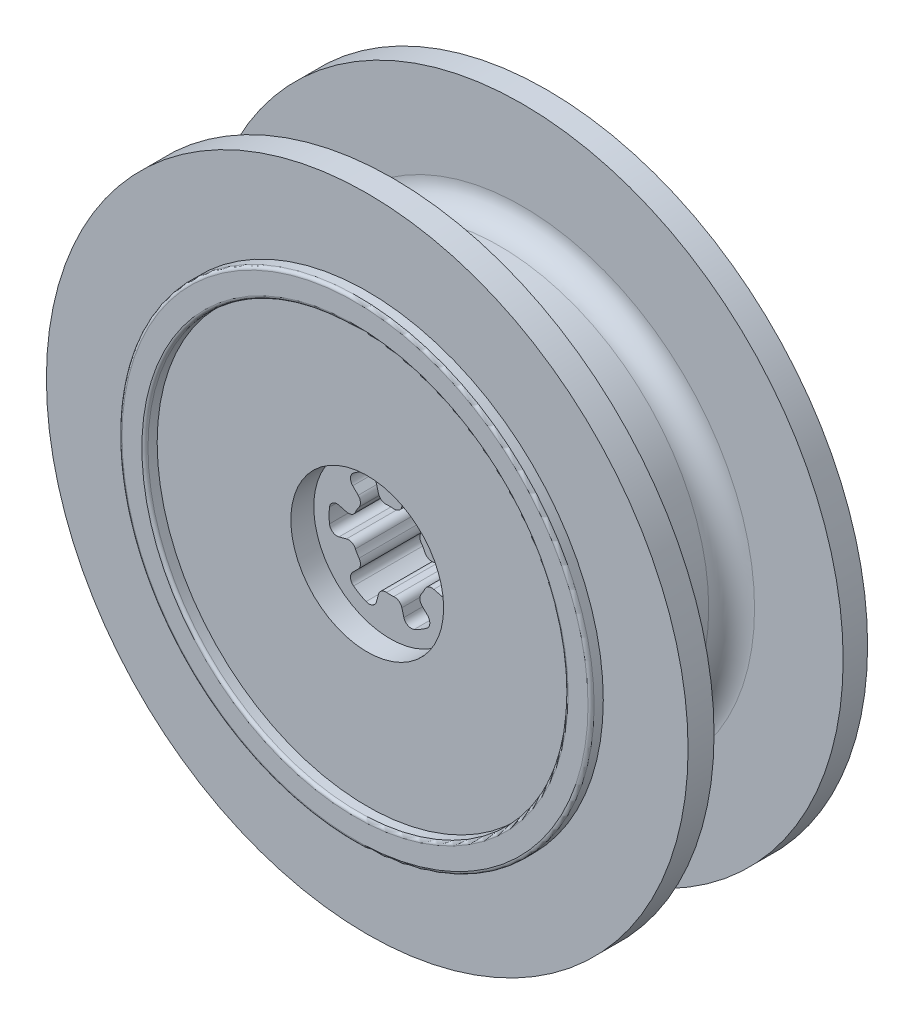
SolidWorks part; units mm, degrees
ref_plane "Front Plane" through (0, 0, 0) normal (0, 0, 1) x (1, 0, 0)
ref_plane "Top Plane" through (0, 0, 0) normal (0, 1, 0) x (1, 0, 0)
ref_plane "Right Plane" through (0, 0, 0) normal (1, 0, 0) x (0, 0, -1)
sketch "Sketch1" plane through (0, 0, 0) normal (0, 0, 1) x (1, 0, 0)
  line L1 (0.647, 2.4148) -> (1.0353, 3.8637)
  line L3 (1.7678, 1.7678) -> (2.8284, 2.8284)
  line L5 (2.4148, 0.647) -> (3.8637, 1.0353)
  line L7 (2.4148, -0.647) -> (3.8637, -1.0353)
  line L9 (1.7678, -1.7678) -> (2.8284, -2.8284)
  line L11 (0.647, -2.4148) -> (1.0353, -3.8637)
  line L13 (-0.647, -2.4148) -> (-1.0353, -3.8637)
  line L15 (-1.7678, -1.7678) -> (-2.8284, -2.8284)
  line L17 (-2.4148, -0.647) -> (-3.8637, -1.0353)
  line L19 (-2.4148, 0.647) -> (-3.8637, 1.0353)
  line L21 (-1.7678, 1.7678) -> (-2.8284, 2.8284)
  line L23 (-0.647, 2.4148) -> (-1.0353, 3.8637)
  circle A0 centre (0, 0) radius 21
  circle A1 centre (0, 0) radius 4
  arc A2 (0.647, 2.4148) -> (-0.647, 2.4148) centre (0, 0) ccw
  arc A3 (2.4148, 0.647) -> (1.7678, 1.7678) centre (0, 0) ccw
  arc A4 (1.7678, -1.7678) -> (2.4148, -0.647) centre (0, 0) ccw
  arc A5 (-0.647, -2.4148) -> (0.647, -2.4148) centre (0, 0) ccw
  arc A6 (-2.4148, -0.647) -> (-1.7678, -1.7678) centre (0, 0) ccw
  arc A7 (-1.7678, 1.7678) -> (-2.4148, 0.647) centre (0, 0) ccw
  circle A8 centre (0, 0) radius 13.75
  circle A9 centre (0, 0) radius 15.45
  point P31 (0, 0)
  dimension "D1" = 42
  dimension "D2" = 8
  dimension "D3" = 2.5
  dimension "D4" = 27.5
  dimension "D5" = 30.9
extrude "Boss-Extrude1" add sketch "Sketch1" along normal blind 1.7 contours A5 L13 A1 L11 | A6 L17 A1 L15 | A7 L21 A1 L19 | A2 L1 A1 L23 | A0 A9 | A9 A8 | A3 L5 A1 L3 | A8 A1 | A4 L9 A1 L7 region at (0, 3.27, 0) region at (2.8319, 1.635, 0) region at (-2.8319, 1.635, 0) region at (2.8319, -1.635, 0) region at (-2.8319, -1.635, 0) region at (0, -3.27, 0) region at (-20.406, 0, 0) region at (-13.3611, 0, 0) region at (-15.013, 0, 0)
extrude "Boss-Extrude2" add sketch "Sketch1<7>" along normal blind 0.75 contours A9 A8 region at (-15.013, 0, 0)
sketch "Sketch1<7>" plane through (0, 0, 0) normal (0, 0, 1) x (1, 0, 0) same geometry as "Sketch1"
sketch "Sketch3" plane through (0, 0, 0) normal (0, 0, -1) x (-1, 0, 0)
  circle A0 centre (0, 0) radius 13.7
  circle A1 centre (0, 0) radius 12
  dimension "D1" = 27.4
  dimension "D2" = 24
extrude "Boss-Extrude3" add sketch "Sketch3" along normal blind 8.45
sketch "Sketch6" plane through (0, 0, -8.45) normal (0, 0, -1) x (-1, 0, 0)
  circle A0 centre (0, 0) radius 21
  circle A1 centre (0, 0) radius 12.0174
extrude "Boss-Extrude5" add sketch "Sketch6" along normal blind 1.6
sketch "Sketch7" plane through (0, 0, 1.7) normal (0, 0, 1) x (1, 0, 0)
  line L0 (0.647, 2.4148) -> (1.0353, 3.8637)
  line L1 (-0.647, 2.4148) -> (-1.0353, 3.8637)
  line L2 (1.7678, 1.7678) -> (2.8284, 2.8284)
  line L3 (1.7678, 1.7678) -> (2.8284, 2.8284) construction
  line L4 (2.4148, 0.647) -> (3.8637, 1.0353)
  line L5 (-1.7678, 1.7678) -> (-2.8284, 2.8284)
  line L6 (-2.4148, 0.647) -> (-3.8637, 1.0353)
  line L7 (-2.4148, -0.647) -> (-3.8637, -1.0353)
  line L8 (-1.7678, -1.7678) -> (-2.8284, -2.8284)
  line L9 (2.4148, -0.647) -> (3.8637, -1.0353)
  line L10 (2.8284, -2.8284) -> (1.7678, -1.7678)
  line L11 (1.7678, -1.7678) -> (2.8284, -2.8284) construction
  line L12 (0.647, -2.4148) -> (1.0353, -3.8637)
  line L13 (-1.0353, -3.8637) -> (-0.647, -2.4148)
  circle A0 centre (0, 0) radius 5
  circle A1 centre (0, 0) radius 2.5
  circle A2 centre (0, 0) radius 4
  arc M1 (0.647, -2.4148) -> (-0.647, -2.4148) centre (0, 0) cw
  line M2 (-0.647, -2.4148) -> (-1.0353, -3.8637)
  arc M3 (-1.0353, -3.8637) -> (-2.8284, -2.8284) centre (0, 0) cw
  line M4 (-2.8284, -2.8284) -> (-1.7678, -1.7678)
  arc M5 (-1.7678, -1.7678) -> (-2.4148, -0.647) centre (0, 0) cw
  line M6 (-2.4148, -0.647) -> (-3.8637, -1.0353)
  arc M7 (-3.8637, -1.0353) -> (-3.8637, 1.0353) centre (0, 0) cw
  line M8 (-3.8637, 1.0353) -> (-2.4148, 0.647)
  arc M9 (-2.4148, 0.647) -> (-1.7678, 1.7678) centre (0, 0) cw
  line M10 (-1.7678, 1.7678) -> (-2.8284, 2.8284)
  arc M11 (-2.8284, 2.8284) -> (-1.0353, 3.8637) centre (0, 0) cw
  line M12 (-1.0353, 3.8637) -> (-0.647, 2.4148)
  arc M13 (-0.647, 2.4148) -> (0.647, 2.4148) centre (0, 0) cw
  line M14 (0.647, 2.4148) -> (1.0353, 3.8637)
  arc M15 (1.0353, 3.8637) -> (2.8284, 2.8284) centre (0, 0) cw
  line M16 (2.8284, 2.8284) -> (1.7678, 1.7678)
  arc M17 (1.7678, 1.7678) -> (2.4148, 0.647) centre (0, 0) cw
  line M18 (2.4148, 0.647) -> (3.8637, 1.0353)
  arc M19 (3.8637, 1.0353) -> (3.8637, -1.0353) centre (0, 0) cw
  line M20 (3.8637, -1.0353) -> (2.4148, -0.647)
  arc M21 (2.4148, -0.647) -> (1.7678, -1.7678) centre (0, 0) cw
  line M22 (1.7678, -1.7678) -> (2.8284, -2.8284)
  arc M23 (2.8284, -2.8284) -> (1.0353, -3.8637) centre (0, 0) cw
  line M24 (1.0353, -3.8637) -> (0.647, -2.4148)
  dimension "D1" = 10
  dimension "D2" = 5
  dimension "D3" = 8
extrude "Boss-Extrude6" add sketch "Sketch7" against normal blind 16.85 contours A0 A2 M19 M23 M3 M7 M11 M15 | A2 M14 M12 M13 | A2 M18 M16 M17 | A2 M22 M20 M21 | A2 M2 M24 M1 | A2 M6 M4 M5 | A2 M10 M8 M9 region at (0, 3.27, 1.7) region at (2.8319, 1.635, 1.7) region at (-2.8319, 1.635, 1.7) region at (2.8319, -1.635, 1.7) region at (-2.8319, -1.635, 1.7) region at (0, -3.27, 1.7) region at (-4.8586, 0, 1.7)
sketch "Sketch8" plane through (0, 0, 0) normal (0, 0, -1) x (-1, 0, 0)
  line L3 (-0.7, 8.0982) -> (-0.7, 11.9796)
  line L4 (-0.7, 11.9796) -> (-0.7, 4.9508)
  line L5 (0.7, 8.0982) -> (0.7, 11.9796)
  line L6 (0.7, 11.9796) -> (0.7, 4.9508)
  line L7 (6.6633, 4.6553) -> (10.0246, 6.596)
  line L8 (10.0246, 6.596) -> (3.9375, 3.0816)
  line L9 (7.3633, 3.4429) -> (10.7246, 5.3836)
  line L10 (10.7246, 5.3836) -> (4.6375, 1.8692)
  line L11 (7.3633, -3.4429) -> (10.7246, -5.3836)
  line L12 (10.7246, -5.3836) -> (4.6375, -1.8692)
  line L13 (6.6633, -4.6553) -> (10.0246, -6.596)
  line L14 (10.0246, -6.596) -> (3.9375, -3.0816)
  line L15 (0.7, -8.0982) -> (0.7, -11.9796)
  line L16 (0.7, -11.9796) -> (0.7, -4.9508)
  line L17 (-0.7, -8.0982) -> (-0.7, -11.9796)
  line L18 (-0.7, -11.9796) -> (-0.7, -4.9508)
  line L19 (-6.6633, -4.6553) -> (-10.0246, -6.596)
  line L20 (-10.0246, -6.596) -> (-3.9375, -3.0816)
  line L21 (-7.3633, -3.4429) -> (-10.7246, -5.3836)
  line L22 (-10.7246, -5.3836) -> (-4.6375, -1.8692)
  line L23 (-7.3633, 3.4429) -> (-10.7246, 5.3836)
  line L24 (-10.7246, 5.3836) -> (-4.6375, 1.8692)
  line L25 (-6.6633, 4.6553) -> (-10.0246, 6.596)
  line L26 (-10.0246, 6.596) -> (-3.9375, 3.0816)
  arc A0 (-10.7246, -5.3836) -> (-10.0246, -6.596) centre (0, 0) ccw
  circle A1 centre (0, 0) radius 12 construction
  circle A2 centre (0, 0) radius 5 construction
  circle A3 centre (0, 0) radius 5 construction
  arc A4 (10.7246, 5.3836) -> (10.0246, 6.596) centre (0, 0) ccw
  arc A5 (0.7, 11.9796) -> (-0.7, 11.9796) centre (0, 0) ccw
  arc A6 (-10.0246, 6.596) -> (-10.7246, 5.3836) centre (0, 0) ccw
  arc A7 (-0.7, -11.9796) -> (0.7, -11.9796) centre (0, 0) ccw
  arc A8 (10.0246, -6.596) -> (10.7246, -5.3836) centre (0, 0) ccw
  point P51 (0, 0)
  circle M27 centre (0, 0) radius 5
  circle M28 centre (0, 0) radius 12
  dimension "D2" = 1.4
  dimension "D3" = 6
extrude "Boss-Extrude7" add sketch "Sketch8" along normal blind 10.04 contours L14 L13 L11 L12 M28 M27 | L10 L9 L7 L8 M28 M27 | L6 L5 L3 L4 M28 M27 | L26 L25 L23 L24 M28 M27 | L22 L21 L19 L20 M28 M27 | L18 L17 L15 L16 M28 M27 region at (0, 8.4884, 0) region at (7.3512, 4.2442, 0) region at (-7.3512, 4.2442, 0) region at (7.3512, -4.2442, 0) region at (-7.3512, -4.2442, 0) region at (0, -8.4884, 0)
sketch "Sketch9" plane through (0, 0, 1.7) normal (0, 0, 1) x (1, 0, 0)
  line L0 (0.647, 2.4148) -> (1.0353, 3.8637)
  line L1 (-1.0353, 3.8637) -> (-0.647, 2.4148)
  line L2 (-1.7678, 1.7678) -> (-2.8284, 2.8284)
  line L3 (-3.8637, 1.0353) -> (-2.4148, 0.647)
  line L4 (-2.4148, -0.647) -> (-3.8637, -1.0353)
  line L5 (-2.8284, -2.8284) -> (-1.7678, -1.7678)
  line L6 (1.7678, 1.7678) -> (2.8284, 2.8284)
  line L7 (2.4148, 0.647) -> (3.8637, 1.0353)
  line L8 (3.8637, -1.0353) -> (2.4148, -0.647)
  line L9 (1.7678, -1.7678) -> (2.8284, -2.8284)
  line L10 (1.7678, -1.7678) -> (2.8284, -2.8284) construction
  line L11 (0.647, -2.4148) -> (1.0353, -3.8637)
  line L13 (-0.647, -2.4148) -> (-1.0353, -3.8637)
  line L15 (-0.647, -2.4148) -> (-1.0353, -3.8637) construction
  line L16 (0.647, -2.4148) -> (1.0353, -3.8637) construction
  circle A0 centre (0, 0) radius 5
  circle A1 centre (0, 0) radius 4
  circle A2 centre (0, 0) radius 2.5
  line M2 (2.8284, 2.8284) -> (1.7678, 1.7678)
  arc M4 (1.7678, 1.7678) -> (2.4148, 0.647) centre (0, 0) cw
  line M6 (2.4148, 0.647) -> (3.8637, 1.0353)
  line M10 (3.8637, -1.0353) -> (2.4148, -0.647)
  arc M12 (2.4148, -0.647) -> (1.7678, -1.7678) centre (0, 0) cw
  line M14 (1.7678, -1.7678) -> (2.8284, -2.8284)
  line M18 (1.0353, -3.8637) -> (0.647, -2.4148)
  arc M20 (0.647, -2.4148) -> (-0.647, -2.4148) centre (0, 0) cw
  line M22 (-0.647, -2.4148) -> (-1.0353, -3.8637)
  line M26 (-2.8284, -2.8284) -> (-1.7678, -1.7678)
  arc M28 (-1.7678, -1.7678) -> (-2.4148, -0.647) centre (0, 0) cw
  line M30 (-2.4148, -0.647) -> (-3.8637, -1.0353)
  line M34 (-3.8637, 1.0353) -> (-2.4148, 0.647)
  arc M36 (-2.4148, 0.647) -> (-1.7678, 1.7678) centre (0, 0) cw
  line M38 (-1.7678, 1.7678) -> (-2.8284, 2.8284)
  line M42 (-1.0353, 3.8637) -> (-0.647, 2.4148)
  arc M44 (-0.647, 2.4148) -> (0.647, 2.4148) centre (0, 0) cw
  line M46 (0.647, 2.4148) -> (1.0353, 3.8637)
  arc M51 (-1.0353, -3.8637) -> (-2.8284, -2.8284) centre (0, 0) cw
  arc M52 (-3.8637, -1.0353) -> (-3.8637, 1.0353) centre (0, 0) cw
  arc M53 (-2.8284, 2.8284) -> (-1.0353, 3.8637) centre (0, 0) cw
  arc M54 (1.0353, 3.8637) -> (2.8284, 2.8284) centre (0, 0) cw
  arc M55 (3.8637, 1.0353) -> (3.8637, -1.0353) centre (0, 0) cw
  arc M56 (2.8284, -2.8284) -> (1.0353, -3.8637) centre (0, 0) cw
  dimension "D1" = 10
  dimension "D2" = 8
  dimension "D3" = 5
extrude "Cut-Extrude1" cut sketch "Sketch9" against normal blind 1.5 contours A1 M22 M18 M20 | A1 M30 M26 M28 | A1 M38 M34 M36 | A1 M46 M42 M44 | A1 M6 M2 M4 | A1 M14 M10 M12 | A0 A1 M55 M56 M51 M52 M53 M54 region at (0, 3.27, 1.7) region at (2.8319, 1.635, 1.7) region at (-2.8319, 1.635, 1.7) region at (2.8319, -1.635, 1.7) region at (-2.8319, -1.635, 1.7) region at (0, -3.27, 1.7) region at (-4.8586, 0, 1.7)
fillet "Fillet2" radius 0.5 24 edges at (3.8637, -1.0353, -7.475) (-3.8637, 1.0353, -7.475) (3.8637, 1.0353, -7.475) (-3.8637, -1.0353, -7.475) (2.8284, 2.8284, -7.475) (-2.8284, -2.8284, -7.475) (1.7678, 1.7678, -7.475) (-1.7678, -1.7678, -7.475) (2.4148, 0.647, -7.475) (-2.4148, -0.647, -7.475) (1.7678, -1.7678, -7.475) (-1.7678, 1.7678, -7.475) (2.8284, -2.8284, -7.475) (-2.8284, 2.8284, -7.475) (1.0353, -3.8637, -7.475) (-1.0353, 3.8637, -7.475) (2.4148, -0.647, -7.475) (-2.4148, 0.647, -7.475) (0.647, -2.4148, -7.475) (-0.647, 2.4148, -7.475) (0.647, 2.4148, -7.475) (-0.647, -2.4148, -7.475) (1.0353, 3.8637, -7.475) (-1.0353, -3.8637, -7.475)
fillet "Fillet3" radius 1.5 2 edges at (-13.7, 0, -8.45) (-13.7, 0, 0)
extrude "Boss-Extrude8" add sketch "Sketch1<9>" along normal blind 2.5 contours A9 A8 region at (-15.013, 0, 0)
sketch "Sketch1<9>" plane through (0, 0, 0) normal (0, 0, 1) x (1, 0, 0) same geometry as "Sketch1"
fillet "Fillet4" radius 0.2 2 edges at (13.75, 0, 2.5) (15.45, 0, 2.5)
equation "\"0.750000mm_1.75\"=0.75"
